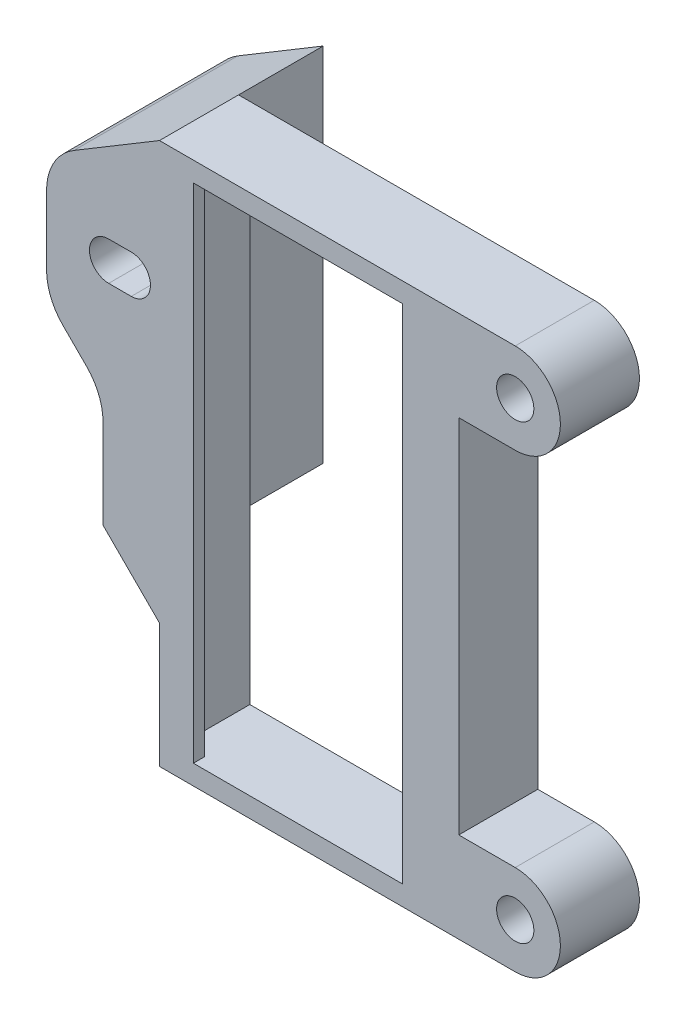
SolidWorks part; units mm, degrees
ref_plane "Plano frontal" through (0, 0, 0) normal (0, 0, 1) x (1, 0, 0)
ref_plane "Plano superior" through (0, 0, 0) normal (0, 1, 0) x (1, 0, 0)
ref_plane "Plano direito" through (0, 0, 0) normal (1, 0, 0) x (0, 0, -1)
sketch "Esboço1" plane through (0, 0, 0) normal (0, 0, 1) x (1, 0, 0)
  line L1 (-9.25, 22.25) -> (9.25, 22.25)
  line L2 (-9.25, 22.25) -> (-9.25, -22.25)
  line L3 (-9.25, -22.25) -> (9.25, -22.25)
  line L4 (9.25, 22.25) -> (9.25, -22.25)
  line L5 (-9.25, 22.25) -> (9.25, -22.25) construction
  line L6 (-9.25, -22.25) -> (9.25, 22.25) construction
  line L7 (-12.25, 24) -> (12.25, 24)
  line L8 (-12.25, 24) -> (-12.25, -24)
  line L9 (-12.25, -24) -> (12.25, -24)
  line L10 (12.25, 24) -> (12.25, -24)
  line L11 (-12.25, 24) -> (12.25, -24) construction
  line L12 (-12.25, -24) -> (12.25, 24) construction
  point P0 (0, 0)
  point P6 (0, 0)
  dimension "D1" = 44.5
  dimension "D2" = 18.5
  dimension "D3" = 3
  dimension "D4" = 48
extrude "Ressalto-extrusão1" add sketch "Esboço1" along normal blind 1
sketch "Esboço2" plane through (0, 0, 1) normal (0, 0, 1) x (1, 0, 0)
  line L0 (19.25, 16) -> (14.25, 16)
  line L1 (12.25, 24) -> (19.25, 24)
  line L2 (11.25, 22.25) -> (11.25, -22.25)
  line L3 (12.25, -24) -> (19.25, -24)
  line L5 (14.25, 16) -> (14.25, -16)
  line L6 (14.25, -16) -> (19.25, -16)
  line L7 (-12.25, 24) -> (12.25, 24)
  line L8 (9.25, -22.25) -> (9.25, 22.25) construction
  line L9 (-11.25, 22.25) -> (11.25, 22.25)
  line L10 (0, 0) -> (12.9455, 0) construction
  line L11 (-12.25, 24) -> (-12.25, -24) construction
  line L12 (9.25, 22.25) -> (-9.25, 22.25) construction
  line L13 (-12.25, 24) -> (-12.25, -24)
  line L14 (11.25, -22.25) -> (-11.25, -22.25)
  line L16 (-12.25, -24) -> (12.25, -24)
  line L17 (-11.25, -22.25) -> (-11.25, 22.25)
  line L18 (-9.25, -22.25) -> (9.25, -22.25) construction
  circle A0 centre (19.25, 20) radius 1.65
  circle A1 centre (19.25, -20) radius 1.65
  arc A3 (19.25, -16) -> (19.25, -24) centre (19.25, -20) cw
  arc A5 (19.25, 24) -> (19.25, 16) centre (19.25, 20) cw
  point P1 (-12.25, -3.46)
  point P12 (11.25, 24)
  point P25 (-12.25, -24.1981)
  point P29 (-12.25, -20.9309)
  point P42 (24.2773, -16)
  dimension "D4" = 3.3
  dimension "D5" = 1
  dimension "D1" = 5
  dimension "D2" = 2
  dimension "D3" = 8
  dimension "D6" = 8
extrude "Ressalto-extrusão2" add sketch "Esboço2" against normal blind 7
sketch "Esboço4" plane through (0, 0, 1) normal (0, 0, 1) x (1, 0, 0)
  line L0 (-12.25, 24) -> (-22.25, 18)
  line L1 (-22.25, 18) -> (-22.25, 7)
  line L2 (-22.25, 7) -> (-17.25, 2)
  line L3 (-17.25, 2) -> (-17.25, -8)
  line L4 (-27.7955, -3) -> (-12.25, -3) construction
  line L5 (-22.25, -24) -> (-12.25, -24)
  line L6 (-12.25, -24) -> (-12.25, 24)
  line L7 (-22.25, -13) -> (-17.25, -8)
  line L8 (-22.25, -24) -> (-22.25, -13)
  line L10 (-16.75, 12.5) -> (-14.75, 12.5) construction
  line L11 (-16.75, 14.2) -> (-14.75, 14.2)
  line L12 (-16.75, 10.8) -> (-14.75, 10.8)
  line L13 (-16.75, -18.5) -> (-14.75, -18.5) construction
  line L14 (-16.75, -20.2) -> (-14.75, -20.2)
  line L15 (-16.75, -16.8) -> (-14.75, -16.8)
  line L17 (-22.25, -13) -> (-9.25, -13) construction
  line L18 (-9.25, 22.25) -> (-9.25, -22.25) construction
  line L19 (-17.25, -8) -> (-12.25, -8)
  arc A0 (-16.75, 14.2) -> (-16.75, 10.8) centre (-16.75, 12.5) ccw
  arc A1 (-14.75, 10.8) -> (-14.75, 14.2) centre (-14.75, 12.5) ccw
  arc A2 (-16.75, -20.2) -> (-16.75, -16.8) centre (-16.75, -18.5) cw
  arc A3 (-14.75, -16.8) -> (-14.75, -20.2) centre (-14.75, -18.5) cw
  circle A5 centre (19.25, -20) radius 1.65 construction
  point P13 (-15.75, 12.5)
  point P20 (-15.75, -18.5)
  point P26 (-15.75, -13)
  point P32 (-22.25, -18.5)
  line M24 (-12.25, 24) -> (-12.25, -24)
  dimension "D7" = 1.7
  dimension "D2" = 45
  dimension "D3" = 18.5
  dimension "D5" = 5
  dimension "D6" = 2
  dimension "D8" = 31
  dimension "D9" = 34
extrude "Ressalto-extrusão3" add sketch "Esboço4" against normal blind 14.5 contours L3 L19 L0 L1 L2 A1 L12 A0 L11 M24 region at (-16.3387, 8.5326, 1)
fillet "Filete1" radius 5 3 edges at (-17.25, 2, -6.25) (-22.25, 18, -6.25) (-22.25, 7, -6.25)
chamfer "Chanfro4" distance 5 angle 45 1 edges at (-12.25, -8, -2.5)
